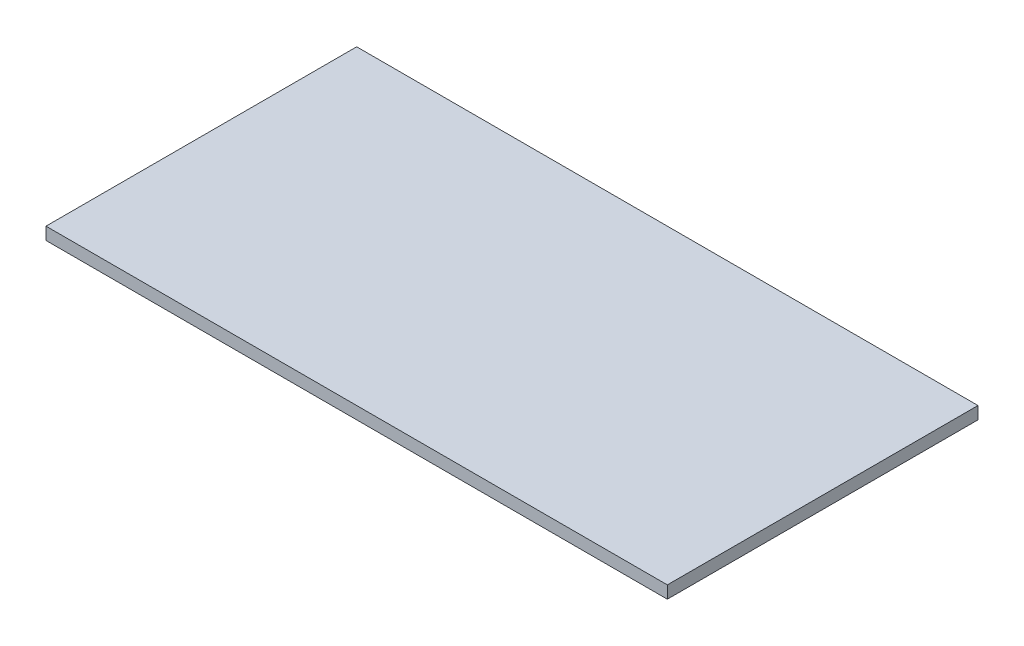
SolidWorks part; units mm, degrees
ref_plane "Front Plane" through (0, 0, 0) normal (0, 0, 1) x (1, 0, 0)
ref_plane "Top Plane" through (0, 0, 0) normal (0, 1, 0) x (1, 0, 0)
ref_plane "Right Plane" through (0, 0, 0) normal (1, 0, 0) x (0, 0, -1)
sketch "Sketch1" plane through (0, 0, 0) normal (0, 1, 0) x (1, 0, 0)
  line L1 (-500, -250) -> (500, -250)
  line L2 (-500, -250) -> (-500, 250)
  line L3 (-500, 250) -> (500, 250)
  line L4 (500, -250) -> (500, 250)
  line L5 (-500, -250) -> (500, 250) construction
  line L6 (-500, 250) -> (500, -250) construction
  point P0 (0, 0)
  dimension "D1" = 1000
  dimension "D2" = 500
extrude "Boss-Extrude1" add sketch "Sketch1" along normal blind 20
